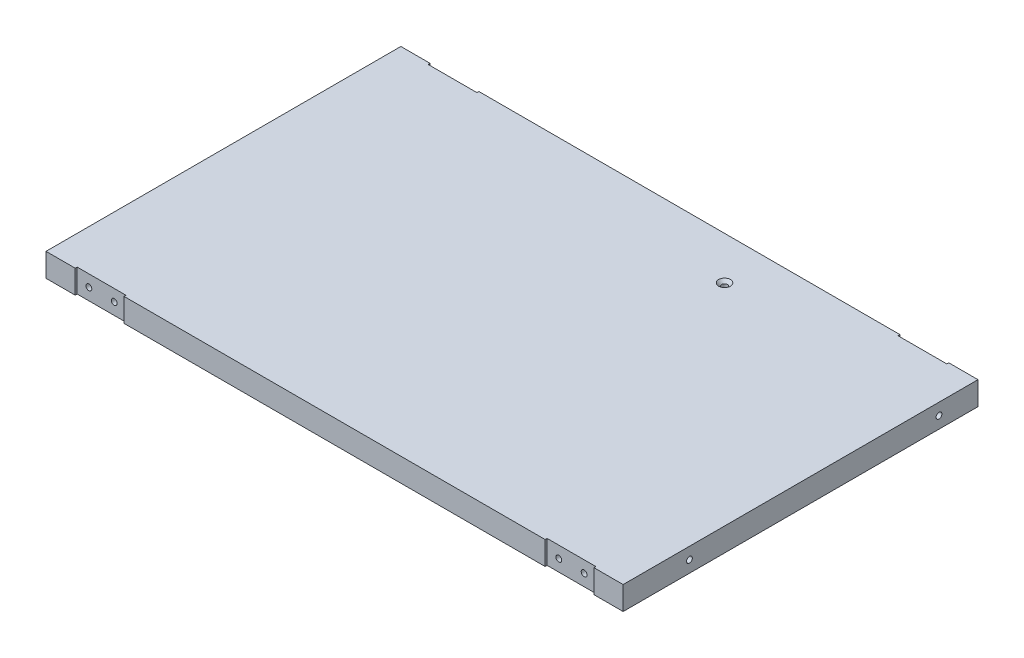
SolidWorks part; units mm, degrees
ref_plane "Front Plane" through (0, 0, 0) normal (0, 0, 1) x (1, 0, 0)
ref_plane "Top Plane" through (0, 0, 0) normal (0, 1, 0) x (1, 0, 0)
ref_plane "Right Plane" through (0, 0, 0) normal (1, 0, 0) x (0, 0, -1)
sketch "Sketch1" plane through (0, 0, 0) normal (0, 1, 0) x (1, 0, 0)
  line L1 (0, 0) -> (296, 0)
  line L2 (0, 0) -> (0, 182)
  line L3 (0, 182) -> (296, 182)
  line L4 (296, 0) -> (296, 182)
  circle A4 centre (188, 160) radius 1.5
  dimension "D12" = 3
  dimension "D1" = 296
  dimension "D2" = 182
  dimension "D13" = 22
  dimension "D14" = 188
extrude "Boss-Extrude1" add sketch "Sketch1" along normal blind 12
sketch "Sketch2" plane through (0, 0, 0) normal (1, 0, 0) x (0, 0, -1)
  line L0 (0, 6) -> (182, 6) construction
  line L1 (0, 12) -> (0, 0) construction
  line L2 (182, 12) -> (182, 0) construction
  circle A0 centre (162, 6) radius 1.5
  circle A1 centre (34, 6) radius 1.5
  dimension "D1" = 3
  dimension "D2" = 3
  dimension "D3" = 20
  dimension "D4" = 148
extrude "Cut-Extrude1" cut sketch "Sketch2" along normal blind 20 from surface starting at face at (0, 6, -91)
extrude "Cut-Extrude2" cut sketch "Sketch2<2>" against normal blind 20 from surface starting at face at (296, 6, -91)
sketch "Sketch2<2>" plane through (0, 0, 0) normal (1, 0, 0) x (0, 0, -1) same geometry as "Sketch2"
sketch "Sketch4" plane through (0, 0, 0) normal (0, 1, 0) x (1, 0, 0)
  circle A0 centre (188, 160) radius 3
  dimension "D1" = 6
extrude "Cut-Extrude3" cut sketch "Sketch4" against normal blind 3 draft 45 from surface starting at face at (148, 12, -91)
sketch "Sketch5" plane through (0, 0, 0) normal (0, 0, 1) x (1, 0, 0)
  line L0 (0, 6) -> (296, 6) construction
  line L1 (0, 12) -> (0, 0) construction
  line L2 (296, 12) -> (296, 0) construction
  circle A0 centre (21, 6) radius 1.5
  circle A1 centre (34, 6) radius 1.5
  circle A2 centre (275, 6) radius 1.5
  circle A3 centre (262, 6) radius 1.5
  dimension "D2" = 3
  dimension "D3" = 3
  dimension "D6" = 3
  dimension "D7" = 3
  dimension "D4" = 21
  dimension "D5" = 13
  dimension "D8" = 21
  dimension "D9" = 13
extrude "Cut-Extrude4" cut sketch "Sketch5" along normal blind 10 from surface starting at face at (148, 6, -182)
extrude "Cut-Extrude5" cut sketch "Sketch5<3>" against normal blind 10
sketch "Sketch5<3>" plane through (0, 0, 0) normal (0, 0, 1) x (1, 0, 0) same geometry as "Sketch5"
sketch "Sketch7" plane through (0, 0, 0) normal (0, 0, 1) x (1, 0, 0)
  line L0 (0, 12) -> (296, 12) construction
  line L1 (15, 12) -> (40, 12)
  line L2 (15, 12) -> (15, 0)
  line L3 (15, 0) -> (40, 0)
  line L4 (40, 12) -> (40, 0)
  line L5 (0, 0) -> (296, 0) construction
  line L7 (281, 12) -> (256, 12)
  line L8 (281, 12) -> (281, 0)
  line L9 (281, 0) -> (256, 0)
  line L10 (256, 12) -> (256, 0)
  dimension "D5" = 15
  dimension "D1" = 25
  dimension "D2" = 12
  dimension "D3" = 25
  dimension "D4" = 12
  dimension "D6" = 15
extrude "Cut-Extrude6" cut sketch "Sketch7" against normal blind 1
extrude "Cut-Extrude7" cut sketch "Sketch7<2>" along normal blind 1 from surface starting at face at (35.5, 6, -182)
sketch "Sketch7<2>" plane through (0, 0, 0) normal (0, 0, 1) x (1, 0, 0) same geometry as "Sketch7"
